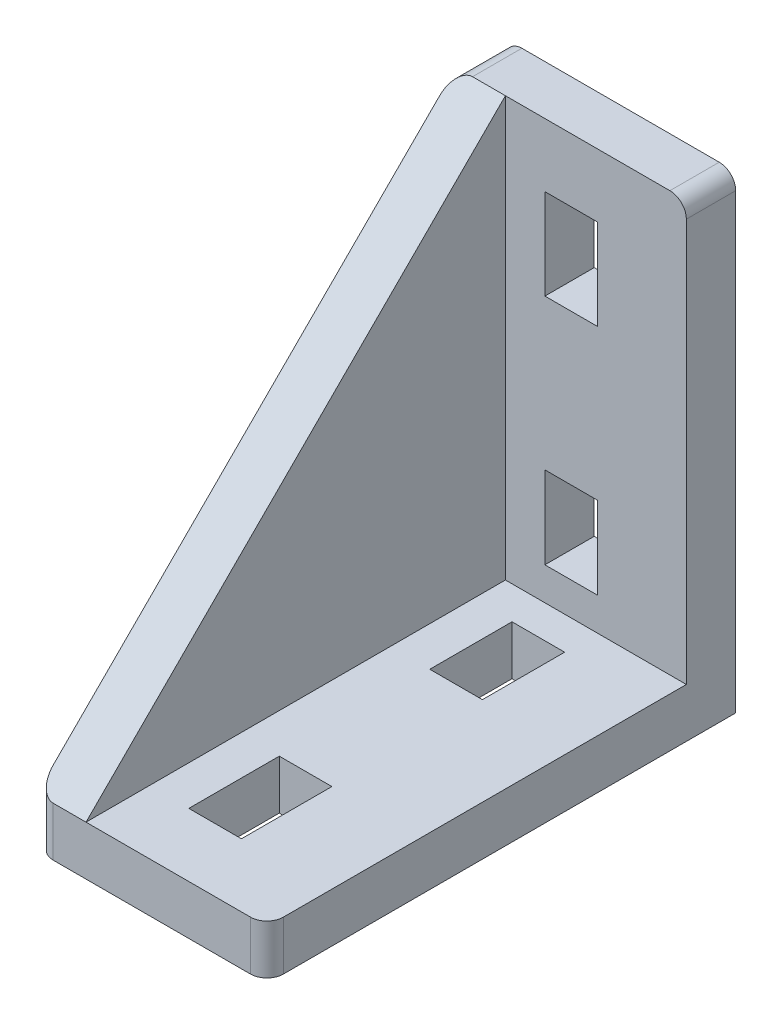
SolidWorks part; units mm, degrees
ref_plane "Alzado" through (0, 0, 0) normal (0, 0, 1) x (1, 0, 0)
ref_plane "Planta" through (0, 0, 0) normal (0, 1, 0) x (1, 0, 0)
ref_plane "Vista lateral" through (0, 0, 0) normal (1, 0, 0) x (0, 0, -1)
sketch "Croquis1" plane through (0, 0, 0) normal (1, 0, 0) x (0, 0, -1)
  line L0 (0, 0) -> (57, 0)
  line L1 (57, 0) -> (57, 57)
  line L7 (0, 6) -> (0, 0)
  line L9 (57, 57) -> (51, 57)
  line L10 (51, 57) -> (0, 6)
  point P5 (0, 0)
  dimension "D1" = 57
  dimension "D2" = 57
  dimension "D3" = 6
  dimension "D4" = 6
extrude "Saliente-Extruir1" add sketch "Croquis1" along normal blind 28 contours L0 L1 region at (0, 20.8245, -36.1755)
shell "Vaciado2" thickness 6 removed face at (14, 57, -54) removed face at (14, 3, 0) removed face at (28, 24, -33) removed face at (14, 31.5, -25.5)
sketch "Croquis2" plane through (0, 0, -51) normal (0, 0, 1) x (1, 0, 0)
  line L0 (0, 57) -> (28, 57) construction
  line L1 (10.8, 49.3) -> (17.2, 49.3)
  line L2 (10.8, 49.3) -> (10.8, 38.3)
  line L3 (10.8, 38.3) -> (17.2, 38.3)
  line L4 (17.2, 49.3) -> (17.2, 38.3)
  line L5 (28, 6) -> (28, 57) construction
  line L6 (28, 57) -> (6, 57) construction
  line L7 (28, 0) -> (0, 0) construction
  line L8 (10.8, 20) -> (17.2, 20)
  line L9 (10.8, 20) -> (10.8, 10)
  line L10 (10.8, 10) -> (17.2, 10)
  line L11 (17.2, 20) -> (17.2, 10)
  point P11 (14, 57)
  point P12 (14, 49.3)
  point P19 (14, 20)
  dimension "D1" = 6.4
  dimension "D2" = 11
  dimension "D3" = 49.3
  dimension "D4" = 20
  dimension "D5" = 10
extrude "Cortar-Extruir1" cut sketch "Croquis2" against normal up to next
sketch "Croquis5" plane through (0, 6, 0) normal (0, 1, 0) x (1, 0, 0)
  line L0 (10.8, 47) -> (17.2, 47)
  line L5 (10.8, 47) -> (10.8, 37)
  line L6 (10.8, 37) -> (17.2, 37)
  line L7 (17.2, 47) -> (17.2, 37)
  line L8 (10.8, 18.7) -> (17.2, 18.7)
  line L9 (10.8, 18.7) -> (10.8, 7.7)
  line L10 (10.8, 7.7) -> (17.2, 7.7)
  line L11 (17.2, 18.7) -> (17.2, 7.7)
  line L12 (0, 57) -> (28, 57) construction
  point P4 (14, 47)
  point P9 (14, 18.7)
  point P10 (14, 57)
  dimension "D1" = 6.4
  dimension "D2" = 10
  dimension "D3" = 11
  dimension "D4" = 20
  dimension "D5" = 49.3
extrude "Cortar-Extruir2" cut sketch "Croquis5" against normal up to next
fillet "Redondeo2" radius 2 4 edges at (0, 3, 0) (28, 3, 0) (0, 57, -54) (28, 57, -54)
